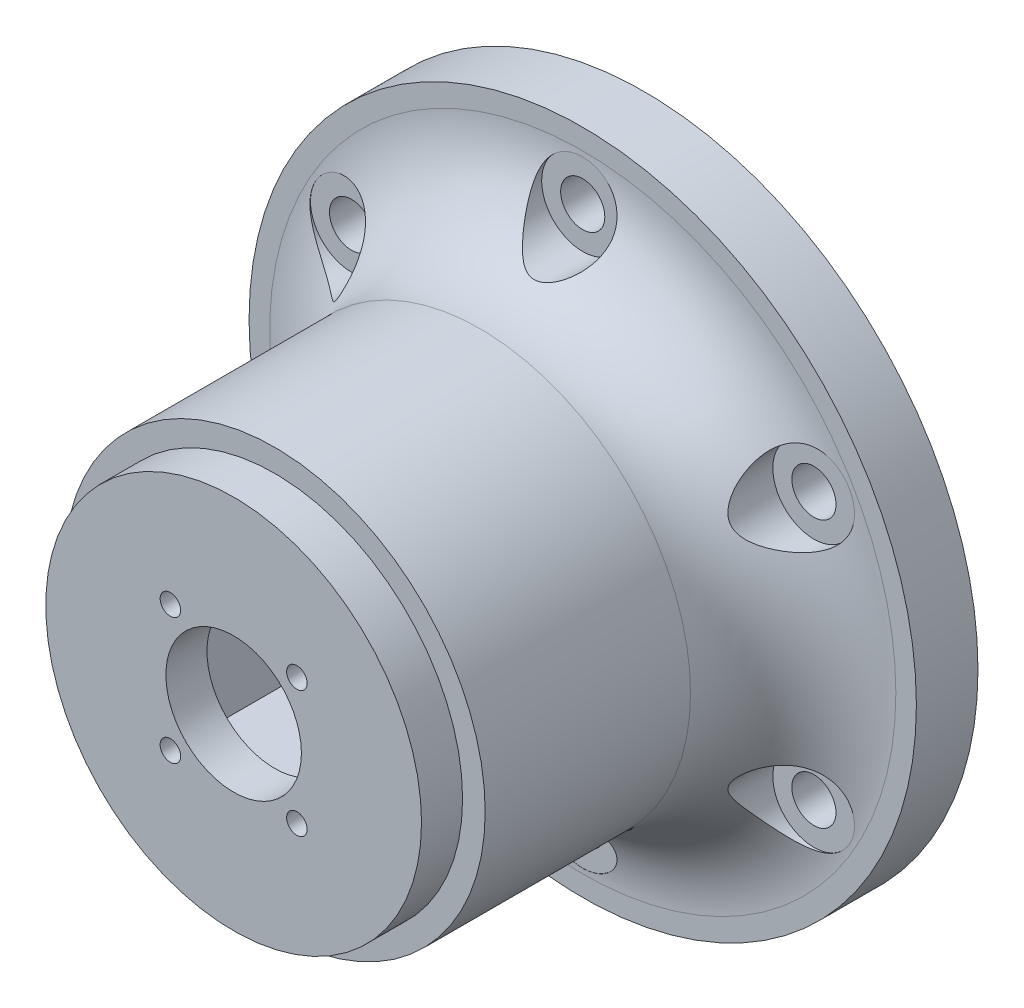
SolidWorks part; units mm, degrees
ref_plane "Front Plane" through (0, 0, 0) normal (0, 0, 1) x (1, 0, 0)
ref_plane "Top Plane" through (0, 0, 0) normal (0, 1, 0) x (1, 0, 0)
ref_plane "Right Plane" through (0, 0, 0) normal (1, 0, 0) x (0, 0, -1)
sketch "Sketch1" plane through (0, 0, 0) normal (0, 0, 1) x (1, 0, 0)
  line L0 (0, 0) -> (0, 32.5) construction
  line L1 (0, 32.5) -> (28.1458, 16.25) construction
  line L2 (28.1458, 16.25) -> (0, 0) construction
  line L3 (0, 0) -> (28.1458, -16.25) construction
  line L4 (28.1458, -16.25) -> (0, -32.5) construction
  line L5 (0, -32.5) -> (0, 0) construction
  line L6 (0, 0) -> (-28.1458, -16.25) construction
  line L7 (-28.1458, -16.25) -> (-28.1458, 16.25) construction
  line L8 (-28.1458, 16.25) -> (0, 0) construction
  line L9 (-28.1458, 16.25) -> (0, 32.5) construction
  line L10 (28.1458, -16.25) -> (28.1458, 16.25) construction
  line L11 (0, -32.5) -> (-28.1458, -16.25) construction
  line L12 (-25.625, 0) -> (-40.625, 0) construction
  line L13 (-12.5, 12.5) -> (12.5, 12.5)
  line L14 (-12.5, 12.5) -> (-12.5, -12.5)
  line L15 (-12.5, -12.5) -> (12.5, -12.5)
  line L16 (12.5, 12.5) -> (12.5, -12.5)
  line L17 (0, 37.5) -> (0, 40.625) construction
  line L18 (22.875, 0) -> (25.625, 0) construction
  line L19 (-7.7, 7.7) -> (7.7, 7.7) construction
  line L20 (-7.7, 7.7) -> (-7.7, -7.7) construction
  line L21 (-7.7, -7.7) -> (7.7, -7.7) construction
  line L22 (7.7, -7.7) -> (7.7, 7.7) construction
  circle A0 centre (0, 0) radius 40.625
  circle A1 centre (0, 32.5) radius 2.6875
  circle A2 centre (28.1458, 16.25) radius 2.6875
  circle A3 centre (28.1458, -16.25) radius 2.6875
  circle A4 centre (0, -32.5) radius 2.6875
  circle A5 centre (-28.1458, -16.25) radius 2.6875
  circle A6 centre (-28.1458, 16.25) radius 2.6875
  circle A7 centre (0, 32.5) radius 5
  circle A8 centre (28.1458, 16.25) radius 5
  circle A9 centre (-28.1458, 16.25) radius 5
  circle A10 centre (-28.1458, -16.25) radius 5
  circle A11 centre (0, -32.5) radius 5
  circle A12 centre (28.1458, -16.25) radius 5
  circle A13 centre (0, 0) radius 8.25
  circle A14 centre (0, 0) radius 25.625
  circle A15 centre (0, 0) radius 22.875
  circle A16 centre (-7.7, 7.7) radius 1.25
  circle A17 centre (7.7, 7.7) radius 1.25
  circle A18 centre (7.7, -7.7) radius 1.25
  circle A19 centre (-7.7, -7.7) radius 1.25
  point P27 (12.5, 0)
  point P28 (-12.5, 0)
  point P29 (0, 12.5)
  point P30 (0, -12.5)
  point P43 (0, 7.7)
  point P44 (0, -7.7)
  point P45 (-7.7, 0)
  point P46 (7.7, 0)
  dimension "D2" = 5.375
  dimension "D3" = 3.125
  dimension "D4" = 10
  dimension "D5" = 16.5
  dimension "D7" = 15
  dimension "D9" = 2.5
  dimension "D1" = 32.5
  dimension "D6" = 25
  dimension "D8" = 2.75
  dimension "D10" = 15.4
extrude "Boss-Extrude1" add sketch "Sketch1" against normal blind 7.5 contours A0 | A1 | A6 | A2 | A5 | A4 | A3 | L15 L16 L13 L14
extrude "Boss-Extrude2" add sketch "Sketch1<3>" along normal offset from surface (42.5 mm away) 50 contours A14 | L13 L16 L15 L14 up to face at (0, 0, -7.5)
sketch "Sketch1<3>" plane through (0, 0, 0) normal (0, 0, 1) x (1, 0, 0) same geometry as "Sketch1"
fillet "Fillet2" radius 12.5 1 edges at (25.625, 0, 0)
extrude "Cut-Extrude1" cut sketch "Sketch1<4>" along normal through all contours A7 | A9 | A8 | A10 | A11 | A12
sketch "Sketch1<4>" plane through (0, 0, 0) normal (0, 0, 1) x (1, 0, 0) same geometry as "Sketch1"
extrude "Boss-Extrude3" add sketch "Sketch1<5>" against normal blind 5 from surface contours L16 L13 L14 L15 A19 A18 A17 A16 A13 region at (0, 12.1464, 0) starting at face at (0, 0, 42.5)
sketch "Sketch1<5>" plane through (0, 0, 0) normal (0, 0, 1) x (1, 0, 0) same geometry as "Sketch1"
extrude "Cut-Extrude2" cut sketch "Sketch1<6>" against normal blind 5 from surface contours A14 A15 region at (-24.9002, 0, 0) starting at face at (25.625, 0, 42.5)
sketch "Sketch1<6>" plane through (0, 0, 0) normal (0, 0, 1) x (1, 0, 0) same geometry as "Sketch1"
